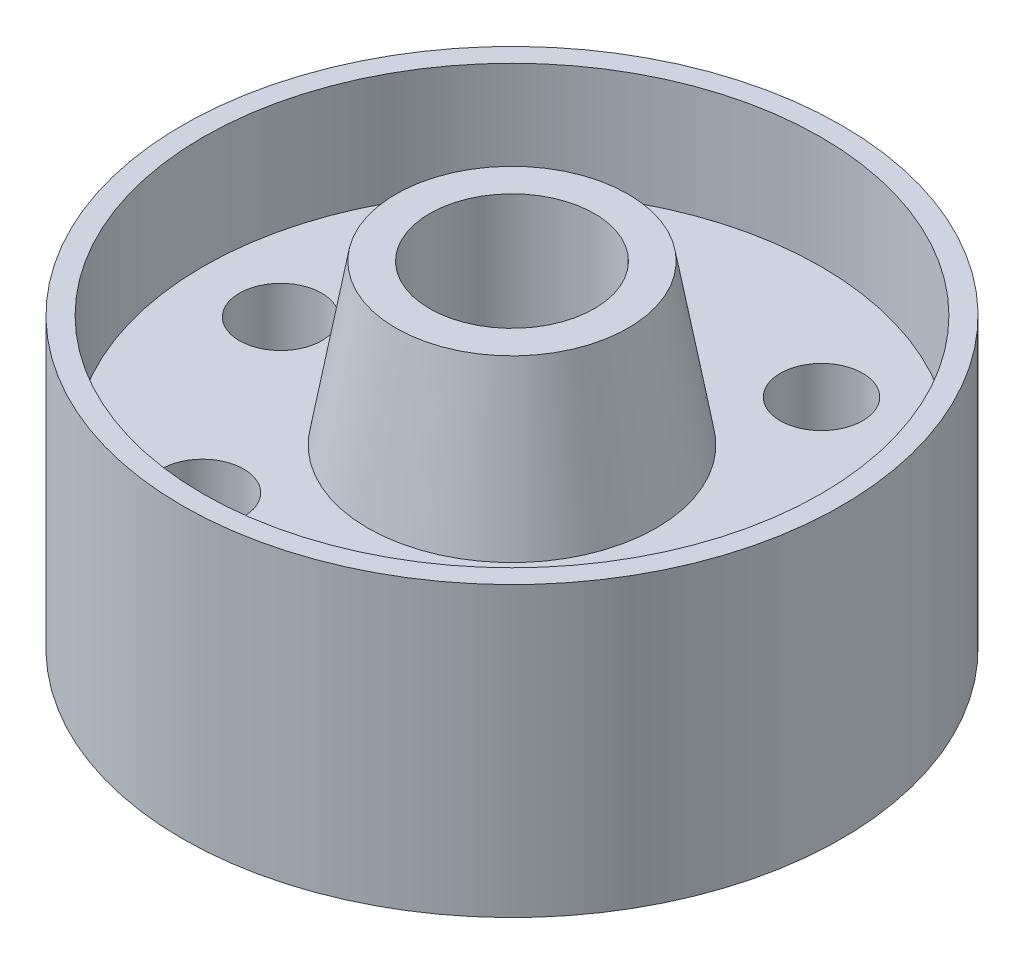
SolidWorks part; units mm, degrees
material "Plain Carbon Steel"
ref_plane "Front Plane" through (0, 0, 0) normal (0, 0, 1) x (1, 0, 0)
ref_plane "Top Plane" through (0, 0, 0) normal (0, 1, 0) x (1, 0, 0)
ref_plane "Right Plane" through (0, 0, 0) normal (1, 0, 0) x (0, 0, -1)
ref_axis "X-axis" through (-88.99, 0, 0) along (1, 0, 0)
ref_axis "Y-axis" through (0, 55, 0) along (0, -1, 0)
ref_axis "Z-axis" through (0, 0, -88.99) along (0, 0, 1)
sketch "Sketch1" plane through (0, 0, 0) normal (1, 0, 0) x (0, 0, -1)
  line L0 (0, 0) -> (-38.1, 0) construction
  line L1 (-38.1, 0) -> (-38.1, 22.098)
  line L2 (-38.1, 22.098) -> (-34.925, 22.098)
  line L3 (-34.925, 22.098) -> (-34.925, 4.826)
  line L4 (-34.925, 4.826) -> (-9.525, 4.826)
  line L5 (-9.525, 4.826) -> (-5.1986, 29.3624)
  line L6 (-5.1986, 29.3624) -> (0, 29.3624)
  line L7 (0, 29.3624) -> (0, -29.3624)
  line L8 (12.7, 29.3624) -> (12.7, 0) construction
  line L9 (-34.925, -4.826) -> (-9.525, -4.826)
  line L10 (-9.525, -4.826) -> (-5.1986, -29.3624)
  line L11 (-34.925, -4.826) -> (-34.925, -22.352)
  line L12 (-34.925, -22.352) -> (-38.1, -22.352)
  line L13 (-5.1986, -29.3624) -> (0, -29.3624)
  line L14 (-38.1, -22.352) -> (-38.1, 0)
  dimension "D1" = 25.4
  dimension "D2" = 10
  dimension "D3" = 29.3624
  dimension "D4" = 4.826
  dimension "D5" = 44.45
  dimension "D6" = 95.25
  dimension "D7" = 101.6
  dimension "D8" = 17.272
  dimension "D9" = 44.45
revolve "Revolve3" add sketch "Sketch1" angle 360 about L8
hole_wizard "1/4 (0.5) Diameter Hole2" positions "Sketch4" profile "Sketch5" hole size "1/4" standard "ANSI Inch" end condition through all
sketch "Sketch4" plane through (0, 4.826, 0) normal (0, 1, 0) x (1, 0, 0)
  line L0 (-17.4625, 42.9459) -> (0, 12.7) construction
  line L1 (0, 12.7) -> (17.4625, 42.9459) construction
  line L2 (17.4625, 42.9459) -> (-17.4625, 42.9459) construction
  line L4 (-34.925, 12.7) -> (-17.4625, -17.5459) construction
  line L5 (-17.4625, -17.5459) -> (0, 12.7) construction
  line L6 (0, 12.7) -> (-34.925, 12.7) construction
  line L9 (34.925, 12.7) -> (17.4625, -17.5459) construction
  line L10 (17.4625, -17.5459) -> (0, 12.7) construction
  line L11 (0, 12.7) -> (34.925, 12.7) construction
  circle A0 centre (0, 12.7) radius 34.925 construction
  point P0 (-17.4625, 42.9459)
  point P2 (17.4625, 42.9459)
  point P4 (34.9156, 11.8897)
  point P6 (17.4625, -17.5459)
  point P8 (-17.4625, -17.5459)
  point P10 (-34.9169, 11.9469)
  dimension "D2" = 69.85
  dimension "D1" = 60
sketch "Sketch5" plane through (-17.4625, 4.826, -42.9459) normal (1, 0, 0) x (0, 0, 1)
  line L0 (0, 0) -> (0, 34.1884)
  line L1 (0, 34.1884) -> (6.35, 34.1884)
  line L2 (6.35, 34.1884) -> (6.35, 0)
  line L5 (6.35, 0) -> (0, 0)
  line L11 (0, -6.35) -> (0, 107.95) construction
  dimension "Thru Hole Dia." = 12.7
  dimension "Thru Hole Depth" = 34.1884
